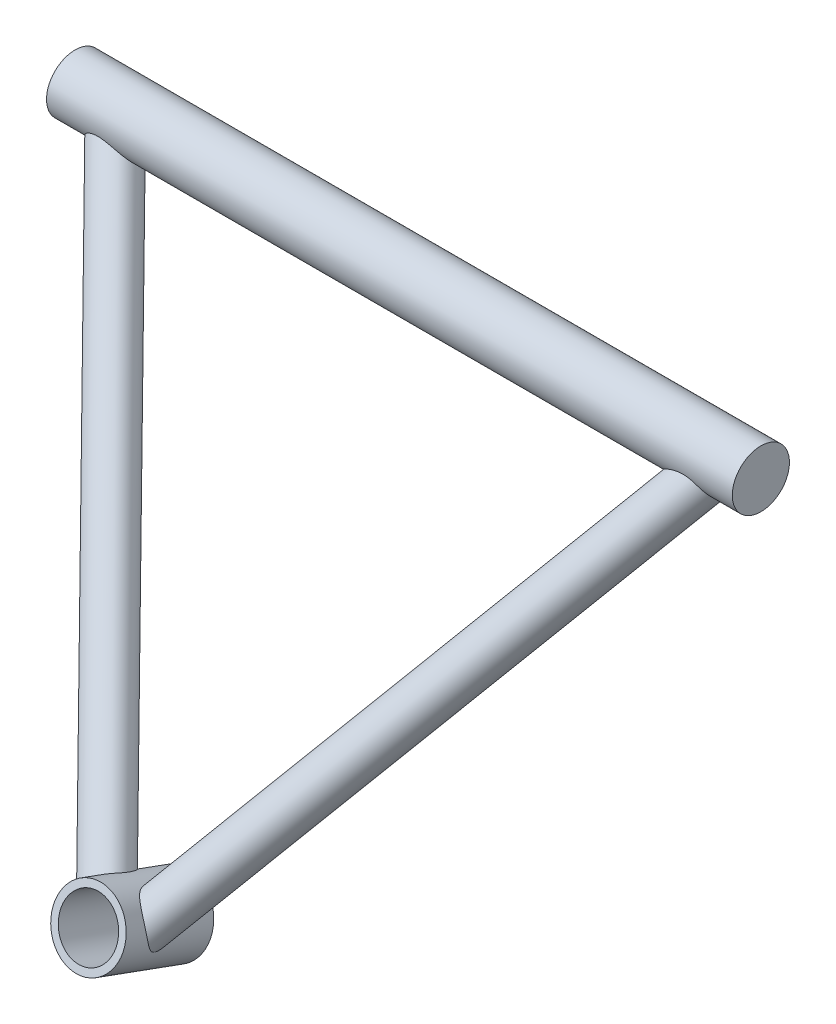
SolidWorks part; units mm, degrees
material "AISI 4130 Steel, normalized at 870C"
ref_plane "Front Plane" through (0, 0, 0) normal (0, 0, 1) x (1, 0, 0)
ref_plane "Top Plane" through (0, 0, 0) normal (0, 1, 0) x (1, 0, 0)
ref_plane "Right Plane" through (0, 0, 0) normal (1, 0, 0) x (0, 0, -1)
sketch "Sketch3" plane through (0, 0, 0) normal (0, 1, 0) x (1, 0, 0)
  line L0 (-5.08, -6.35) -> (5.08, -6.35) construction
  line L2 (0, -88.2205) -> (0, 88.2205) construction
  line L3 (5.08, 0) -> (-5.08, 0) construction
  dimension "D1" = 5.08
  dimension "D2" = 10.16
  dimension "D3" = 6.35
  dimension "D4" = 10.16
  dimension "D5" = 5.08
ref_plane "Plane1" through (0, 3.0363, 4.1033) normal (0, 0.5948, 0.8039) x (1, 0, 0)
ref_plane "Plane3" through (0, 0, 0) normal (0, 0.342, 0.9397) x (-1, 0, 0)
sketch "Sketch1" plane through (0, 0, 0) normal (0, 0.342, 0.9397) x (1, 0, 0)
  circle A0 centre (0, 0) radius 15.875
  dimension "D1" = 31.75
extrude "Boss-Extrude1" add sketch "Sketch1" along normal mid plane 41.402 contours A0
sketch "Sketch4" plane through (0, 3.0363, 4.1033) normal (0, 0.5948, 0.8039) x (1, 0, 0)
  line L0 (-5.08, -3.7771) -> (-138.43, 227.1919)
  line L2 (0, -91.114) -> (0, 91.114) construction
  dimension "D2" = 30
  dimension "D3" = 266.7
sweep "Sweep1" add path "Sketch4" circular profile diameter 19.05 parameters "D3"=19.05
sketch "Sketch15" plane through (0, 3.0363, 4.1033) normal (0, 0.5948, 0.8039) x (1, 0, 0)
  line L0 (5.08, -3.7771) -> (138.43, 227.1919)
  line L1 (0, -91.114) -> (0, 91.114) construction
  dimension "D1" = 266.7
  dimension "D2" = 30
sweep "Sweep2" add path "Sketch15" circular profile diameter 19.05 parameters "D3"=19.05
sketch "Sketch36" plane through (-132.9845, 185.157, -137.009) normal (-0.5, 0.6962, -0.5151) x (0.8657, 0.3847, -0.3203)
  circle A0 centre (-6.4314, -4.9225) radius 7.9375
  dimension "D1" = 15.875
extrude "Cut-Extrude2" cut sketch "Sketch36" against normal up to surface (285.2397 mm away) up to face at (14.717, 3.5589, -7.6245)
sketch "Sketch37" plane through (132.9845, 185.157, -137.009) normal (0.5, 0.6962, -0.5151) x (0.8657, -0.3847, 0.3203)
  circle A0 centre (6.4314, -4.9225) radius 7.9375
  dimension "D1" = 15.875
extrude "Cut-Extrude3" cut sketch "Sketch37" against normal up to surface (253.7133 mm away) up to face at (0.1193, -14.2693, 7.2095)
sketch "Sketch77" plane through (0, 7.0802, 19.4526) normal (0, 0.342, 0.9397) x (1, 0, 0)
  circle A1 centre (0, 0) radius 15.875
extrude "Boss-Extrude2" add sketch "Sketch77" against normal up to surface (41.402 mm away) up to face at (0, -21.9978, -14.023)
sketch "Sketch2" plane through (0, -7.0802, -19.4526) normal (0, -0.342, -0.9397) x (-1, 0, 0)
  circle A0 centre (0, 0) radius 12.7
  dimension "D1" = 25.4
extrude "Cut-Extrude1" cut sketch "Sketch2" against normal up to next
ref_plane "Plane2" through (0, 0, -127) normal (0, 0, 1) x (1, 0, 0)
ref_plane "Plane4" through (0, 177.8, 0) normal (0, 1, 0) x (1, 0, 0)
sketch "Sketch40" plane through (-106.934, 0, -127) normal (0, 0, 1) x (1, 0, 0)
  line L0 (108.4431, 182.88) -> (50108.4431, 182.88) construction
  line L1 (-45.466, 182.88) -> (259.334, 182.88)
  point P0 (106.934, 182.88)
  point P1 (106.934, 182.88)
  dimension "D1" = 304.8
  dimension "D5" = 182.88
sweep "Sweep5" add path "Sketch40" circular profile diameter 25.4 parameters "D3"=25.4
